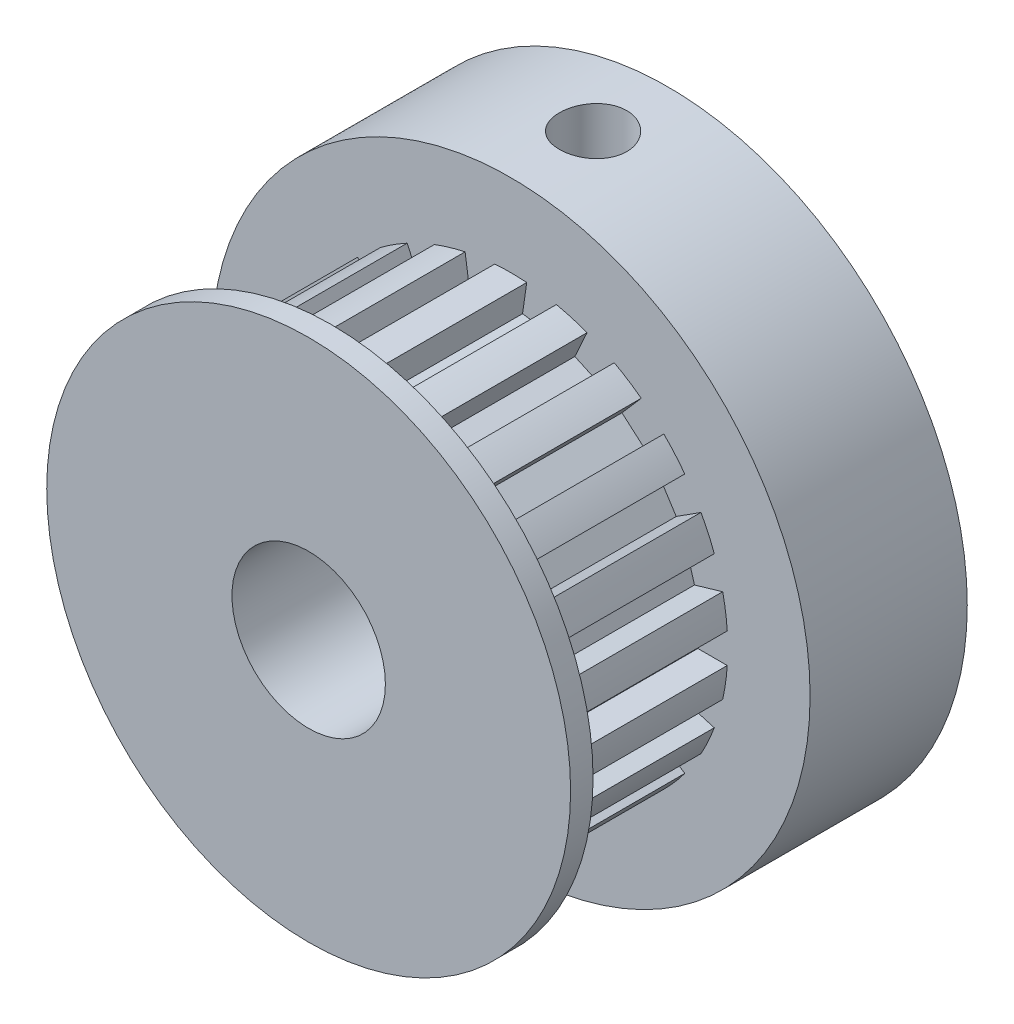
SolidWorks part; units mm, degrees
ref_plane "Front Plane" through (0, 0, 0) normal (0, 0, 1) x (1, 0, 0)
ref_plane "Top Plane" through (0, 0, 0) normal (0, 1, 0) x (1, 0, 0)
ref_plane "Right Plane" through (0, 0, 0) normal (1, 0, 0) x (0, 0, -1)
sketch "Sketch1" plane through (0, 0, 0) normal (0, 0, 1) x (1, 0, 0)
  circle A0 centre (0, 0) radius 8.89
  dimension "D1" = 17.78
extrude "Boss-Extrude1" add sketch "Sketch1" against normal blind 0.762
sketch "Sketch2" plane through (0, 0, -0.762) normal (0, 0, -1) x (-1, 0, 0)
  circle A0 centre (0, 0) radius 7.366
  dimension "D1" = 14.732
extrude "Boss-Extrude2" add sketch "Sketch2" along normal blind 6.096
sketch "Sketch3" plane through (0, 0, -6.858) normal (0, 0, -1) x (-1, 0, 0)
  circle A0 centre (0, 0) radius 10.16
  dimension "D1" = 20.32
extrude "Boss-Extrude3" add sketch "Sketch3" along normal blind 5.334
sketch "Sketch4" plane through (0, 0, 0) normal (0, 0, 1) x (1, 0, 0)
  circle A0 centre (0, 0) radius 2.6035
  dimension "D1" = 5.207
extrude "Cut-Extrude1" cut sketch "Sketch4" against normal blind 25.654
ref_plane "Plane2" through (-7.366, 0, 0) normal (-1, 0, 0) x (0, 0, 1)
sketch "Sketch5" plane through (-7.366, 0, 0) normal (-1, 0, 0) x (0, 0, 1)
  line L0 (-6.858, -7.366) -> (-6.858, 7.366) construction
  line L1 (-6.858, 0.508) -> (-0.762, 0.508)
  line L2 (-6.858, 0.508) -> (-6.858, -0.508)
  line L3 (-6.858, -0.508) -> (-0.762, -0.508)
  line L4 (-0.762, 0.508) -> (-0.762, -0.508)
  line L5 (-0.762, 7.366) -> (-0.762, -7.366) construction
  point P8 (-6.858, 0)
  dimension "D1" = 1.016
extrude "Cut-Extrude2" cut sketch "Sketch5" against normal blind 1.016
ref_axis "Axis1" through (0, 0, -12.192) along (0, 0, 1)
pattern_circular "CirPattern1" count 22 over 360 about axis through (0, 0, -12.192) along (0, 0, 1) of "Cut-Extrude2"
sketch "Sketch6" plane through (0, 0, 0) normal (0, 1, 0) x (1, 0, 0)
  line L0 (10.16, 12.192) -> (-10.16, 12.192) construction
  circle A0 centre (0, 9.652) radius 1.143
  dimension "D1" = 2.286
  dimension "D2" = 2.54
extrude "Cut-Extrude3" cut sketch "Sketch6" against normal blind 22.098 and the other way blind 22.098
